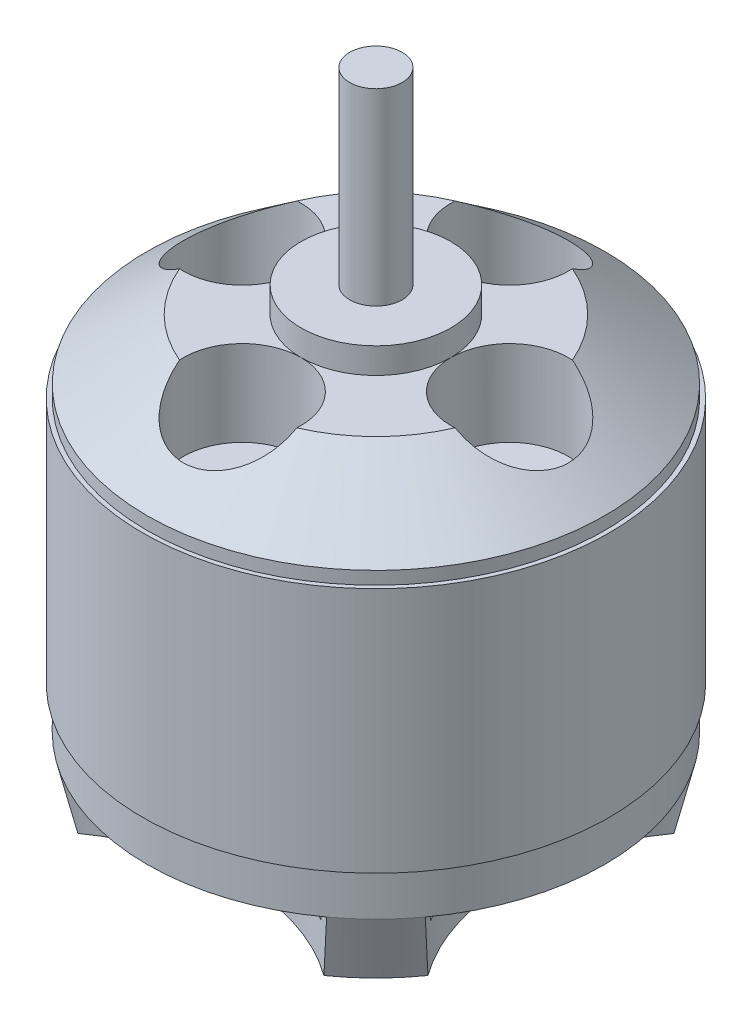
SolidWorks part; units mm, degrees
material "Plain Carbon Steel"
ref_plane "Front" through (0, 0, 0) normal (0, 0, 1) x (1, 0, 0)
ref_plane "Top" through (0, 0, 0) normal (0, 1, 0) x (1, 0, 0)
ref_plane "Right" through (0, 0, 0) normal (1, 0, 0) x (0, 0, -1)
sketch "Sketch1" plane through (0, 0, 0) normal (0, 0, 1) x (1, 0, 0)
  line L0 (0, 11.176) -> (1.5558, 11.176)
  line L1 (0, -50) -> (0, 50) construction
  line L2 (1.5558, 11.176) -> (1.5558, 0)
  line L3 (50, 0) -> (-50, 0) construction
  line L4 (1.5558, 0) -> (4.445, 0)
  line L5 (4.445, 0) -> (4.445, -1.524)
  line L6 (4.445, -1.524) -> (8.89, -1.524)
  line L7 (8.89, -1.524) -> (13.589, -5.08)
  line L8 (13.589, -5.08) -> (13.589, -5.842)
  line L9 (13.589, -5.842) -> (13.843, -5.842)
  line L10 (13.843, -5.842) -> (13.843, -20.4724)
  line L11 (13.589, -20.4724) -> (13.589, -23.0124)
  line L12 (13.589, -23.0124) -> (12.7, -26.67)
  line L13 (12.7, -26.67) -> (3.81, -26.67)
  line L14 (3.81, -26.67) -> (3.81, -26.924)
  line L15 (3.81, -26.924) -> (1.5558, -26.924)
  line L16 (1.5558, -26.924) -> (1.5558, -28.956)
  line L17 (1.5558, -28.956) -> (0, -28.956)
  line L18 (0, -28.956) -> (0, 11.176)
  line L19 (13.589, -20.4724) -> (13.843, -20.4724)
  dimension "D1" = 13.843
  dimension "D2" = 1.5557
  dimension "D3" = 11.176
  dimension "D4" = 4.445
  dimension "D5" = 1.524
  dimension "D6" = 8.89
  dimension "D7" = 4.318
  dimension "D8" = 0.762
  dimension "D9" = 0.254
  dimension "D10" = 14.6304
  dimension "D11" = 2.54
  dimension "D12" = 25.146
  dimension "D13" = 12.7
  dimension "D14" = 3.81
  dimension "D15" = 0.254
  dimension "D16" = 40.132
revolve "Revolve1" add sketch "Sketch1" angle 360 about L18
sketch "Sketch2" plane through (0, -1.524, 0) normal (0, 1, 0) x (1, 0, 0)
  circle A0 centre (0, 7.9375) radius 3.4925
  circle A1 centre (7.9375, 0) radius 3.4925
  circle A2 centre (0, -7.9375) radius 3.4925
  circle A3 centre (-7.9375, 0) radius 3.4925
  circle A5 centre (0, 0) radius 4.445 construction
  circle A7 centre (0, 0) radius 4.445 construction
  dimension "D2" = 6.985
extrude "Cut-Extrude1" cut sketch "Sketch2" against normal blind 5.08
sketch "Sketch3" plane through (0, -26.67, 0) normal (0, -1, 0) x (1, 0, 0)
  line L1 (-7.3025, 10.3905) -> (7.3025, 10.3905) construction
  circle A0 centre (0, 20.4866) radius 12.4602
  circle A1 centre (-20.4866, 0) radius 12.4602
  circle A2 centre (0, -20.4866) radius 12.4602
  circle A3 centre (20.4866, 0) radius 12.4602
  circle A4 centre (0, 0) radius 8.0264 construction
  circle A5 centre (0, 0) radius 12.7 construction
  dimension "D1" = 16.0528
  dimension "D2" = 14.605
extrude "Cut-Extrude2" cut sketch "Sketch3" against normal offset from surface (3.6576 mm away) 2.54 up to face at (0, -20.4724, -13.843)
sketch "Sketch4" plane through (0, -23.0124, 0) normal (0, -1, 0) x (1, 0, 0)
  circle A0 centre (0, 0) radius 12.1158
  arc A2 (8.0324, 10.9609) -> (-8.0324, 10.9609) centre (0, 0) ccw construction
  dimension "D1" = 1.4732
extrude "Cut-Extrude3" cut sketch "Sketch4" against normal blind 2.54 and the other way blind 1.27
hole_wizard "#4-40 Tapped Hole1" positions "Sketch7" profile "Sketch6" tap size "#4-40" standard "ANSI Inch"
sketch "Sketch7" plane through (0, -26.67, 0) normal (0, -1, 0) x (-1, 0, 0)
  line L0 (6.6723, 6.6723) -> (-6.6723, -6.6723) construction
  line L2 (5.6665, -5.6665) -> (-5.6665, 5.6665) construction
  line L5 (0, 0) -> (0, -19.5936) construction
  point P16 (5.6665, -5.6665)
  point P18 (-6.6723, -6.6723)
  point P20 (-5.6665, 5.6665)
  point P22 (6.6723, 6.6723)
  dimension "D1" = 18.8722
  dimension "D2" = 16.0274
  dimension "D3" = 45
sketch "Sketch6" plane through (-5.6665, -26.67, 5.6665) normal (1, 0, 0) x (0, 0, -1)
  line L0 (0, 0) -> (0, 3.2192)
  line L1 (0, 3.2192) -> (1.1303, 2.54)
  line L2 (1.1303, 2.54) -> (1.1303, 0.3937)
  line L3 (1.1303, 0.3937) -> (1.524, 0)
  line L5 (1.524, 0) -> (0, 0)
  line L6 (-1.1303, 0.3937) -> (-1.524, 0) construction
  line L10 (0, 3.2192) -> (-1.1303, 2.54) construction
  line L11 (0, -6.35) -> (0, 107.95) construction
  dimension "Tap Drill Dia." = 2.2606
  dimension "Tap Drill Depth" = 2.54
  dimension "Near C'Sink Dia." = 3.048
  dimension "Near C'Sink Angle" = 90
  dimension "Drill Angle" = 118
cosmetic thread "Hole Thread7" parameters "D1"=2.0853, "D2"=2.8448
cosmetic thread "Hole Thread8" parameters "D1"=2.0853, "D2"=2.8448
cosmetic thread "Hole Thread9" parameters "D1"=2.0853, "D2"=2.8448
cosmetic thread "Hole Thread10" parameters "D1"=2.0853, "D2"=2.8448
